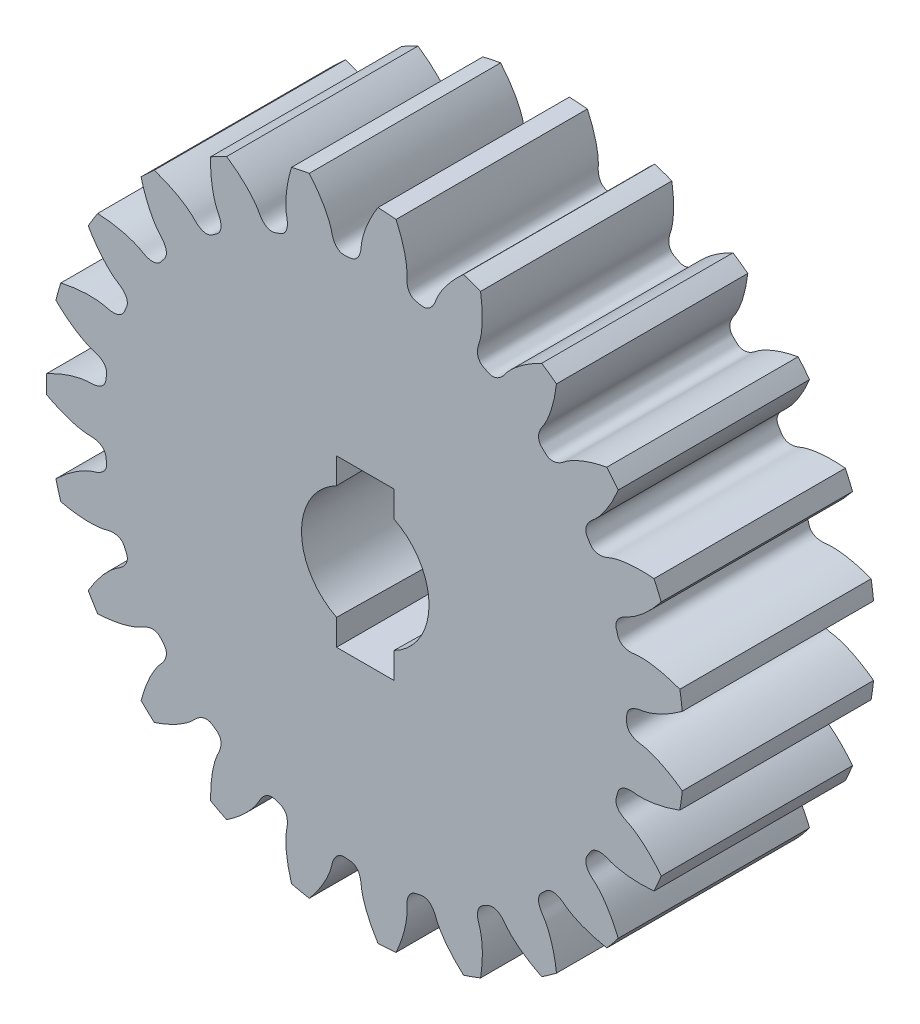
SolidWorks part; units mm, degrees
ref_plane "Front Plane" through (0, 0, 0) normal (0, 0, 1) x (1, 0, 0)
ref_plane "Top Plane" through (0, 0, 0) normal (0, 1, 0) x (1, 0, 0)
ref_plane "Right Plane" through (0, 0, 0) normal (1, 0, 0) x (0, 0, -1)
ref_axis "Axis1" through (0, 0, 55) along (0, 0, -1)
sketch "旋转草图小直齿轮" plane through (0, 0, 0) normal (1, 0, 0) x (0, 0, -1)
  line L0 (0, 0) -> (1, 0) construction
  line L1 (-7.5, 0) -> (-7.5, 25)
  line L2 (-7.5, 25) -> (7.5, 25)
  line L3 (7.5, 25) -> (7.5, 0)
  line L4 (7.5, 0) -> (-7.5, 0)
  dimension "Side1" = 7.5
  dimension "OutsideRadius" = 25
  dimension "Side2" = 7.5
revolve "小直齿轮" add sketch "旋转草图小直齿轮" angle 360 about L0
sketch "齿草图小直齿轮" plane through (0, 0, 0) normal (0, 0, 1) x (1, 0, 0)
  arc A0 (24.9469, 2.7677) -> (24.9469, -2.7677) centre (0, 0) cw
  spline S0 degree 3 poles (24.9469, -2.7677) (24.6681, -2.5585) (24.2954, -2.3016) (23.8243, -2.0186) (23.5696, -1.8756) (23.3275, -1.7489) (23.0987, -1.6377) (22.8839, -1.541) (22.6838, -1.4579) (22.4989, -1.3874) (22.3298, -1.3286) (22.177, -1.2805) (22.041, -1.242) (21.9223, -1.2121) (21.821, -1.1898) (21.6782, -1.1625) (21.549, -1.1472) (21.4313, -1.1224) (21.3769, -1.1096) (21.3235, -1.0956) (21.2713, -1.0804) (21.2201, -1.0639) (21.1699, -1.046) (21.1206, -1.0266) (21.0721, -1.0056) (21.0244, -0.9828) (20.9773, -0.958) (20.9309, -0.9309) (20.885, -0.9013) (20.8397, -0.8688) (20.795, -0.8329) (20.7511, -0.7931) (20.7081, -0.7488) (20.6665, -0.6995) (20.6271, -0.6446) (20.5906, -0.5837) (20.5582, -0.5165) (20.5315, -0.4433) (20.5118, -0.3648) (20.5012, -0.2878) (20.4966, -0.1658) (20.5025, 0) (20.4966, 0.1658) (20.5012, 0.2878) (20.5118, 0.3648) (20.5315, 0.4433) (20.5582, 0.5165) (20.5906, 0.5837) (20.6271, 0.6446) (20.6665, 0.6995) (20.7081, 0.7488) (20.7511, 0.7931) (20.795, 0.8329) (20.8397, 0.8688) (20.885, 0.9013) (20.9309, 0.9309) (20.9773, 0.958) (21.0244, 0.9828) (21.0721, 1.0056) (21.1206, 1.0266) (21.1699, 1.046) (21.2201, 1.0639) (21.2713, 1.0804) (21.3235, 1.0956) (21.3769, 1.1096) (21.4313, 1.1224) (21.549, 1.1472) (21.6782, 1.1625) (21.821, 1.1898) (21.9223, 1.2121) (22.041, 1.242) (22.177, 1.2805) (22.3298, 1.3286) (22.4989, 1.3874) (22.6838, 1.4579) (22.8839, 1.541) (23.0987, 1.6377) (23.3275, 1.7489) (23.5696, 1.8756) (23.8243, 2.0186) (24.2954, 2.3016) (24.6681, 2.5585) (24.9469, 2.7677) knots 0 0 0 0 0.094201 0.122209 0.14852 0.173133 0.196048 0.217267 0.236787 0.25461 0.270736 0.285165 0.297895 0.308929 0.318265 0.325903 0.34824 0.353362 0.3584 0.363363 0.36826 0.373101 0.377899 0.382666 0.38742 0.392177 0.396959 0.40179 0.406696 0.411708 0.416859 0.422185 0.427725 0.433517 0.439595 0.445983 0.452694 0.459717 0.467016 0.474526 0.480668 0.5 0.519332 0.525474 0.532984 0.540283 0.547306 0.554017 0.560405 0.566483 0.572275 0.577815 0.583141 0.588292 0.593304 0.59821 0.603041 0.607823 0.61258 0.617334 0.622101 0.626899 0.63174 0.636637 0.6416 0.646638 0.65176 0.674097 0.681735 0.691071 0.702105 0.714835 0.729264 0.74539 0.763213 0.782733 0.803952 0.826867 0.85148 0.877791 0.905799 1 1 1 1
extrude "齿拉伸切除小直齿轮" cut sketch "齿草图小直齿轮" against normal blind 7.5 and the other way blind 7.5
pattern_circular "齿形小直齿轮" count 23 every 15.652 about axis through (0, 0, 55) along (0, 0, -1) of "齿拉伸切除小直齿轮"
sketch "孔旋转草图" plane through (0, 0, 0) normal (1, 0, 0) x (0, 0, -1)
  line L0 (0, 0) -> (1, 0) construction
  line L1 (-7.5, 0) -> (7.5, 0)
  line L2 (7.5, 0) -> (7.5, 5.2)
  line L3 (7.5, 5.2) -> (-7.5, 5)
  line L4 (-7.5, 5) -> (-7.5, 0)
  dimension "BoreSide1" = 7.5
  dimension "TaperSide1" = 5.2
  dimension "BoreSide2" = 7.5
  dimension "TaperSide2" = 5
revolve "孔旋转切除" cut sketch "孔旋转草图" angle 360 about L0
sketch "辅助草图小直齿轮" plane through (0, 0, 0) normal (0, 0, 1) x (1, 0, 0)
  circle A0 centre (0, 0) radius 23 construction
  circle A1 centre (0, 0) radius 21.6129 construction
  circle A2 centre (0, 0) radius 21.6806 construction
  circle A3 centre (0, 0) radius 25 construction
  circle A4 centre (0, 0) radius 20.5 construction
  dimension "PitchDiameter" = 46
  dimension "BaseDiameter" = 43.2259
  dimension "FormDiameter" = 43.3611
  dimension "MajorDiameter" = 50
  dimension "MinorDiameter" = 41
sketch "Sketch5" plane through (0, 0, 7.5) normal (0, 0, 1) x (1, 0, 0)
  line L0 (0, 0) -> (9.5577, 18.1345)
  spline S0 degree 3 poles (9.0384, 23.3089) (9.0868, 23.0028) (9.1363, 22.5918) (9.1685, 22.0819) (9.1782, 21.79) (9.1793, 21.5167) (9.1728, 21.2624) (9.1599, 21.0272) (9.1416, 20.8113) (9.1191, 20.6147) (9.0935, 20.4376) (9.0659, 20.2798) (9.0376, 20.1413) (9.0094, 20.0221) (8.9827, 19.922) (8.9412, 19.7826) (8.8953, 19.6608) (8.8633, 19.5449) (8.8496, 19.4907) (8.8375, 19.4369) (8.8269, 19.3835) (8.8181, 19.3305) (8.8108, 19.2777) (8.8054, 19.225) (8.8017, 19.1722) (8.8, 19.1194) (8.8004, 19.0662) (8.803, 19.0125) (8.8082, 18.9582) (8.8162, 18.903) (8.8276, 18.8468) (8.8427, 18.7894) (8.8622, 18.7309) (8.8868, 18.6713) (8.9174, 18.611) (8.9548, 18.5506) (8.9995, 18.491) (9.0522, 18.4335) (9.1129, 18.3799) (9.1764, 18.3351) (9.2826, 18.2749) (9.4325, 18.2039) (9.577, 18.1224) (9.6874, 18.0703) (9.7606, 18.0443) (9.8394, 18.0257) (9.9167, 18.0157) (9.9912, 18.0135) (10.0622, 18.0179) (10.1291, 18.0277) (10.1919, 18.0419) (10.251, 18.0597) (10.3066, 18.0804) (10.359, 18.1036) (10.4087, 18.1288) (10.4561, 18.1559) (10.5015, 18.1847) (10.5452, 18.2151) (10.5874, 18.247) (10.6283, 18.2804) (10.6682, 18.3152) (10.7072, 18.3516) (10.7454, 18.3894) (10.783, 18.4288) (10.8199, 18.4697) (10.8563, 18.5122) (10.9326, 18.6052) (11.0056, 18.7129) (11.0955, 18.8272) (11.1619, 18.9068) (11.2431, 18.9985) (11.3398, 19.1016) (11.4528, 19.215) (11.5828, 19.3381) (11.7304, 19.4699) (11.8963, 19.6093) (12.081, 19.7555) (12.285, 19.9075) (12.5089, 20.0642) (12.753, 20.2246) (13.1881, 20.4924) (13.5524, 20.6889) (13.8304, 20.8259) knots 0.010439 0.010439 0.010439 0.010439 0.094201 0.122209 0.14852 0.173133 0.196048 0.217267 0.236787 0.25461 0.270736 0.285165 0.297895 0.308929 0.318265 0.325903 0.34824 0.353362 0.3584 0.363363 0.36826 0.373101 0.377899 0.382666 0.38742 0.392177 0.396959 0.40179 0.406696 0.411708 0.416859 0.422185 0.427725 0.433517 0.439595 0.445983 0.452694 0.459717 0.467016 0.474526 0.480668 0.5 0.519332 0.525474 0.532984 0.540283 0.547306 0.554017 0.560405 0.566483 0.572275 0.577815 0.583141 0.588292 0.593304 0.59821 0.603041 0.607823 0.61258 0.617334 0.622101 0.626899 0.63174 0.636637 0.6416 0.646638 0.65176 0.674097 0.681735 0.691071 0.702105 0.714835 0.729264 0.74539 0.763213 0.782733 0.803952 0.826867 0.85148 0.877791 0.905799 0.989561 0.989561 0.989561 0.989561 construction
sketch "Sketch6" plane through (0, 0, 7.5) normal (0, 0, 1) x (1, 0, 0)
  line L1 (-2.25, 6.5) -> (2.25, 6.5)
  line L2 (-2.25, 6.5) -> (-2.25, -6.5)
  line L3 (-2.25, -6.5) -> (2.25, -6.5)
  line L4 (2.25, 6.5) -> (2.25, -6.5)
  line L5 (-2.25, 6.5) -> (2.25, -6.5) construction
  line L6 (-2.25, -6.5) -> (2.25, 6.5) construction
  point P0 (0, 0)
  point P5 (0, 6.5)
  dimension "D1" = 4.5
  dimension "D2" = 6.5
extrude "Extrude1" cut sketch "Sketch6" against normal through all
